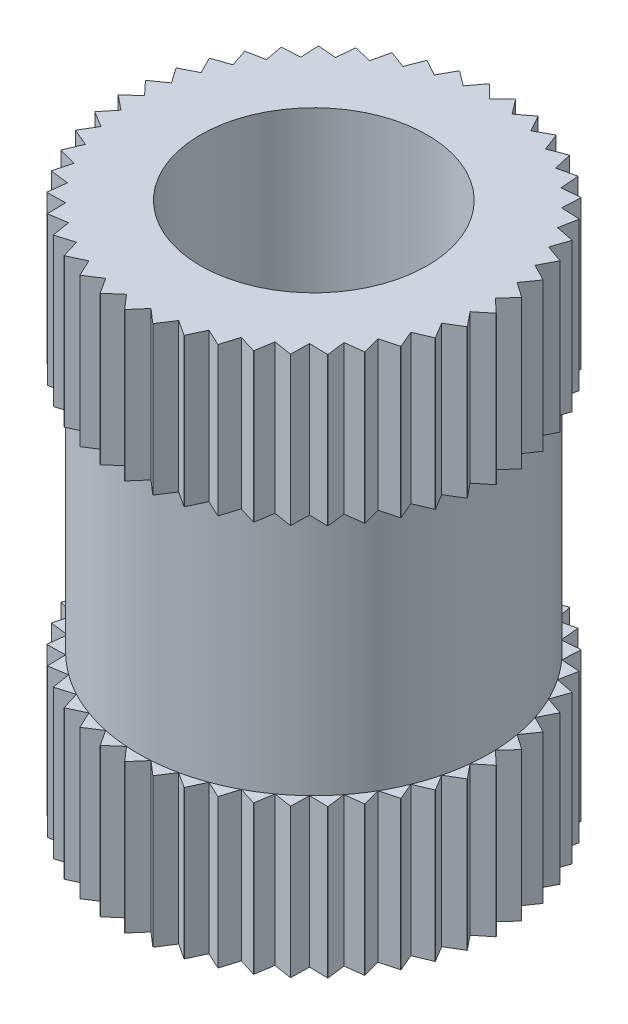
SolidWorks part; units mm, degrees
material "Brass"
ref_plane "Front Plane" through (0, 0, 0) normal (0, 0, 1) x (1, 0, 0)
ref_plane "Top Plane" through (0, 0, 0) normal (0, 1, 0) x (1, 0, 0)
ref_plane "Right Plane" through (0, 0, 0) normal (1, 0, 0) x (0, 0, -1)
sketch "Sketch1" plane through (0, 0, 0) normal (0, 0, 1) x (1, 0, 0)
  line L0 (0, 0) -> (0, 14.9316) construction
  line L1 (0, 0) -> (0, 10)
  line L2 (0, 10) -> (-3.5, 10)
  line L3 (-3.5, 10) -> (-3.5, 7.25)
  line L4 (-3.5, 7.25) -> (-3.25, 7.25)
  line L5 (-3.25, 7.25) -> (-3.25, 2.75)
  line L6 (-3.25, 2.75) -> (-3.5, 2.75)
  line L7 (-3.5, 2.75) -> (-3.5, 0)
  line L8 (-3.5, 0) -> (0, 0)
  dimension "D1" = 7
  dimension "D2" = 10
  dimension "D3" = 2.75
  dimension "D4" = 2.75
  dimension "D5" = 0.25
revolve "Revolve1" add sketch "Sketch1" angle 360 about L0
sketch "Sketch2" plane through (0, 10, 0) normal (0, 1, 0) x (1, 0, 0)
  line L0 (0, 3.25) -> (0.2416, 3.4916)
  line L1 (0, 3.25) -> (-0.2416, 3.4916)
  circle A0 centre (0, 0) radius 3.5
  circle A1 centre (0, 0) radius 3.25
  dimension "D1" = 0.25
  dimension "D2" = 7
extrude "Cut-Extrude1" cut sketch "Sketch2" against normal through all contours L1 L0 region at (0, 10, -3.4148)
ref_axis "Axis1" through (0, 6.3, 0) along (0, -1, 0)
pattern_circular "CirPattern1" count 45 over 360 about axis through (0, 6.3, 0) along (0, -1, 0) of "Cut-Extrude1"
hole_wizard "M5x0.8 Tapped Hole1" positions "Sketch3" profile "Sketch4" tap size "M5x0.8" standard "ANSI Metric" end condition through all
sketch "Sketch3" plane through (0, 10, 0) normal (0, 1, 0) x (1, 0, 0)
  point P0 (0, 0)
sketch "Sketch4" plane through (0, 10, 0) normal (1, 0, 0) x (0, 0, 1)
  line L0 (0, 0) -> (0, 10)
  line L1 (0, 10) -> (2.1, 10)
  line L2 (2.1, 10) -> (2.1, 0)
  line L5 (2.1, 0) -> (0, 0)
  line L11 (0, -6.35) -> (0, 107.95) construction
  dimension "Thru Tap Drill Dia." = 4.2
  dimension "Thru Tap Drill Depth" = 10
cosmetic thread "Hole Thread1" parameters "D2"=5
